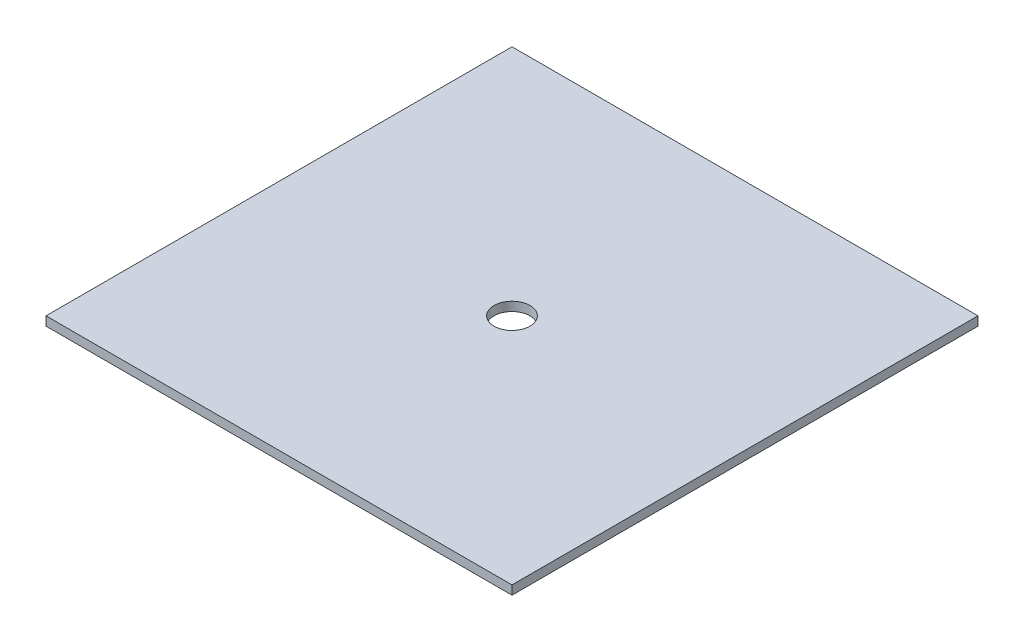
SolidWorks part; units mm, degrees
ref_plane "Front Plane" through (0, 0, 0) normal (0, 0, 1) x (1, 0, 0)
ref_plane "Top Plane" through (0, 0, 0) normal (0, 1, 0) x (1, 0, 0)
ref_plane "Right Plane" through (0, 0, 0) normal (1, 0, 0) x (0, 0, -1)
sketch "Sketch1" plane through (0, 0, 0) normal (0, 1, 0) x (1, 0, 0)
  line L1 (6.5, -6.5) -> (-6.5, -6.5)
  line L2 (6.5, -6.5) -> (6.5, 6.5)
  line L3 (6.5, 6.5) -> (-6.5, 6.5)
  line L4 (-6.5, -6.5) -> (-6.5, 6.5)
  line L5 (6.5, -6.5) -> (-6.5, 6.5) construction
  line L6 (6.5, 6.5) -> (-6.5, -6.5) construction
  point P0 (0, 0)
  dimension "D1" = 13
  dimension "D2" = 13
extrude "Mesh" add sketch "Sketch1" along normal blind 0.25
sketch "Sketch2" plane through (0, 0.25, 0) normal (0, 1, 0) x (1, 0, 0)
  circle A0 centre (0, 0) radius 0.5
  dimension "D1" = 1
extrude "Hole" cut sketch "Sketch2" against normal blind 10 and the other way blind 10
